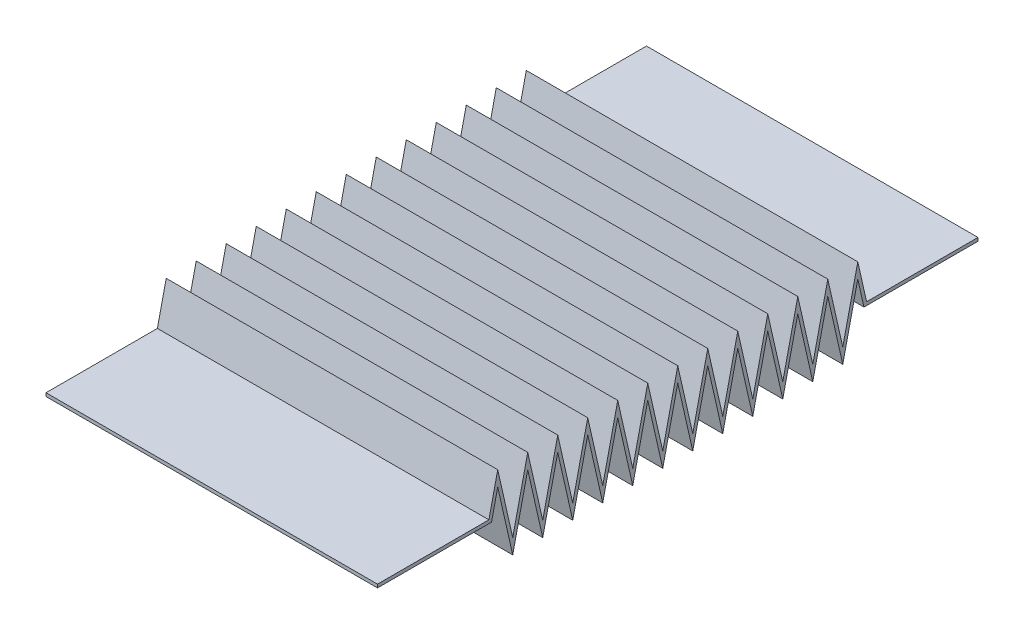
SolidWorks part; units mm, degrees
ref_plane "Front Plane" through (0, 0, 0) normal (0, 0, 1) x (1, 0, 0)
ref_plane "Top Plane" through (0, 0, 0) normal (0, 1, 0) x (1, 0, 0)
ref_plane "Right Plane" through (0, 0, 0) normal (1, 0, 0) x (0, 0, -1)
sketch "Sketch2" plane through (0, 0, 0) normal (0, 0, 1) x (1, 0, 0)
  line L1 (-27.5, 10) -> (27.5, 10)
  line L2 (-27.5, 10) -> (-27.5, 0)
  line L3 (-27.5, 0) -> (27.5, 0)
  line L4 (27.5, 10) -> (27.5, 0)
  point P4 (0, 0)
  dimension "D1" = 10
  dimension "D2" = 55
sketch "Sketch3" plane through (0, 0, 0) normal (1, 0, 0) x (0, 0, -1)
  line L0 (0, 10) -> (90.571, 10) construction
  line L1 (0, 0) -> (90.571, 0) construction
  line L2 (90.571, 5.25) -> (90.571, -12.75) construction
  line L3 (17, 5) -> (18.1314, 10)
  line L4 (18.1314, 10) -> (20.3943, 0)
  line L5 (20.3943, 0) -> (22.6571, 10)
  line L6 (22.6571, 10) -> (24.9199, 0)
  line L7 (24.9199, 0) -> (27.1828, 10)
  line L8 (27.1828, 10) -> (29.4456, 0)
  line L9 (29.4456, 0) -> (31.7085, 10)
  line L10 (31.7085, 10) -> (33.9713, 0)
  line L11 (33.9713, 0) -> (36.2341, 10)
  line L12 (36.2341, 10) -> (38.497, 0)
  line L13 (38.497, 0) -> (40.7598, 10)
  line L14 (40.7598, 10) -> (43.0226, 0)
  line L15 (43.0226, 0) -> (45.2855, 10)
  line L16 (45.2855, 10) -> (47.5483, 0)
  line L17 (47.5483, 0) -> (49.8112, 10)
  line L18 (49.8112, 10) -> (52.074, 0)
  line L19 (0, 10) -> (0, 0) construction
  line L20 (52.074, 0) -> (54.3368, 10)
  line L21 (54.3368, 10) -> (56.5997, 0)
  line L22 (56.5997, 0) -> (58.8625, 10)
  line L23 (58.8625, 10) -> (61.1254, 0)
  line L24 (61.1254, 0) -> (63.3882, 10)
  line L25 (63.3882, 10) -> (65.651, 0)
  line L26 (65.651, 0) -> (67.9139, 10)
  line L27 (67.9139, 10) -> (70.1767, 0)
  line L28 (70.1767, 0) -> (72.4396, 10)
  line L29 (72.4396, 10) -> (73.571, 5)
  line L30 (90.571, 10) -> (90.571, 0) construction
  line L31 (17, 5) -> (0, 5)
  line L32 (73.571, 5) -> (90.571, 5)
  dimension "D2" = 17
  dimension "D1" = 10
  dimension "D3" = 17
extrude "Extrude-Thin1" add sketch "Sketch3" against normal mid plane 50 thin thin type mid plane wall 0.5
